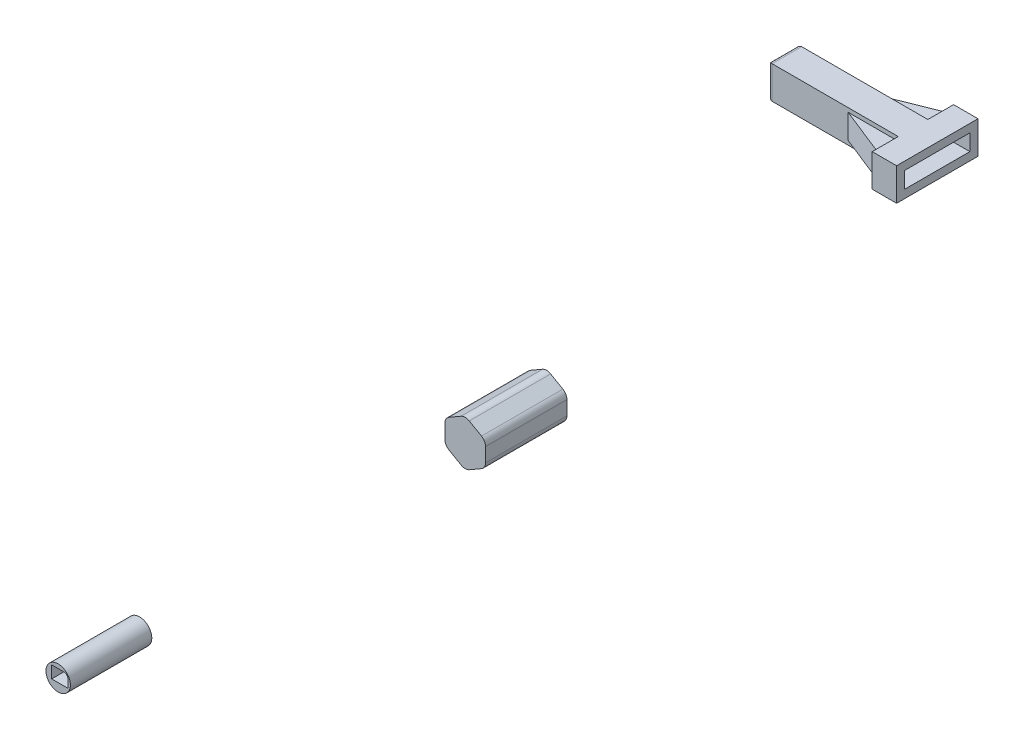
SolidWorks part; units mm, degrees
ref_plane "前视基准面" through (0, 0, 0) normal (0, 0, 1) x (1, 0, 0)
ref_plane "上视基准面" through (0, 0, 0) normal (0, 1, 0) x (1, 0, 0)
ref_plane "右视基准面" through (0, 0, 0) normal (1, 0, 0) x (0, 0, -1)
other "Configuration Table"
sketch "草图6" plane through (0, 0, 0) normal (0, 0, 1) x (1, 0, 0)
  line L0 (-10, 21.1505) -> (-10, -19.1334) construction
  line L1 (-5, 6) -> (-2, 6)
  line L2 (-5, 6) -> (-5, 2)
  line L3 (-5, 2) -> (-2, 2)
  line L4 (-2, 6) -> (-2, 2)
  dimension "D1" = 4
  dimension "D2" = 3
  dimension "D3" = 2
  dimension "D4" = 2
  dimension "D5" = 5
sketch "草图7" plane through (0, 0, 0) normal (1, 0, 0) x (0, 0, -1)
  line L0 (0, 0) -> (0, 6.7847)
  line L1 (0, 21.1505) -> (0, -19.1334) construction
  line L2 (4.0685, 10.336) -> (17.5151, 17.8868)
  arc A0 (0, 6.7847) -> (4.0685, 10.336) centre (0, 10.8908) ccw
  arc A1 (17.5151, 17.8868) -> (28.1001, 5.9227) centre (21.516, 10.762) cw
ref_plane "基准面1" through (0, 0, 50) normal (0, 0, 1) x (1, 0, 0)
ref_plane "基准面2" through (0, 0, 100) normal (0, 0, 1) x (1, 0, 0)
sketch "草图8" plane through (0, 0, 100) normal (0, 0, 1) x (1, 0, 0)
  circle A2 centre (-5, 0) radius 1.5
  point P0 (0, 0)
  dimension "D1" = 3
  dimension "D2" = 5
sketch "草图9" plane through (0, 0, 50) normal (0, 0, 1) x (1, 0, 0)
  line L0 (-2, 6) -> (-2, 2) construction
  line L7 (-5, 2.8868) -> (-7.5, 1.4434)
  line L8 (-7.5, 1.4434) -> (-7.5, -1.4434)
  line L9 (-7.5, -1.4434) -> (-5, -2.8868)
  line L10 (-5, -2.8868) -> (-2.5, -1.4434)
  line L11 (-2.5, -1.4434) -> (-2.5, 1.4434)
  line L12 (-2.5, 1.4434) -> (-5, 2.8868)
  circle A0 centre (-5, 0) radius 2.5 construction
  point P1 (-2.5396, -1.5)
  dimension "D1" = 5
extrude "凸台-拉伸2" add sketch "草图8" along normal blind 10 contours A2
sketch "草图10" plane through (0, 0, 110) normal (0, 0, 1) x (1, 0, 0)
  line L1 (-5.8, 1) -> (-4.3, 1)
  line L2 (-5.8, 1) -> (-5.8, -0.5)
  line L3 (-5.8, -0.5) -> (-3.8, -0.5)
  line L4 (-3.8, 0.5) -> (-3.8, -0.5)
  arc A0 (-3.8, 0.5) -> (-4.3, 1) centre (-4.3, 0.5) ccw
  point P7 (-3.8, 1)
  dimension "D5" = 0.5
  dimension "D1" = 2
  dimension "D2" = 1.5
  dimension "D3" = 3.8
  dimension "D4" = 1
extrude "切除-拉伸1" cut sketch "草图10" against normal blind 10
extrude "凸台-拉伸3" add sketch "草图9" along normal blind 10 separate body
fillet "圆角1" radius 1 1 edges at (-5, 2.8868, 55)
fillet "圆角2" radius 1 5 edges at (-2.5, -1.4434, 55) (-5, -2.8868, 55) (-7.5, -1.4434, 55) (-7.5, 1.4434, 55) (-2.5, 1.4434, 55)
extrude "凸台-拉伸4" add sketch "草图6" along normal blind 10 separate body contours L1 L4 L3 L2
sketch "草图14" plane through (-5, 0, 0) normal (-1, 0, 0) x (0, 0, 1)
  line L1 (3.1661, 6) -> (6.7951, 6)
  line L2 (3.1661, 6) -> (3.1661, 2)
  line L3 (3.1661, 2) -> (6.7951, 2)
  line L4 (6.7951, 6) -> (6.7951, 2)
  dimension "D1" = 4
  dimension "D2" = 3.629
  dimension "D3" = 3.1661
  dimension "D4" = 2
extrude "凸台-拉伸5" add sketch "草图14" along normal blind 16
fillet "圆角3" radius 0.5 4 edges at (-21, 4, 6.7951) (-21, 6, 4.9806) (-21, 4, 3.1661) (-21, 2, 4.9806)
sketch "草图20" plane through (-21, 0, 0) normal (-1, 0, 0) x (0, 0, 1)
  circle A0 centre (4.9806, 3.9861) radius 0.1125
  dimension "D1" = 0.2251
  dimension "D2" = 3.9861
  dimension "D3" = 4.9806
extrude "切除-拉伸2" cut sketch "草图20" against normal blind 16
ref_plane "基准面4" through (0, 4, 0) normal (0, -1, 0) x (-1, 0, 0)
sketch "草图23" plane through (0, 4, 0) normal (0, -1, 0) x (-1, 0, 0)
  line L0 (5, -0.7096) -> (11.1492, -3.1661)
  line L1 (5, -3.1661) -> (5, 0) construction
  line L2 (20.5, -3.1661) -> (5, -3.1661) construction
  line L3 (3.1943, -5) -> (18.6145, -5) construction
rib "筋5" sketch "草图23" sketch "草图23" thickness 3 extrusion direction parallel to sketch draft on no parameters "D1"=3
ref_plane "基准面5" through (0, 0, 4.9806) normal (0, 0, 1) x (1, 0, 0)
mirror "镜向4" about plane through (0, 0, 4.9806) normal (0, 0, 1) of "筋5"
shell "抽壳8" thickness 1 removed face at (-2, 4, 5)
